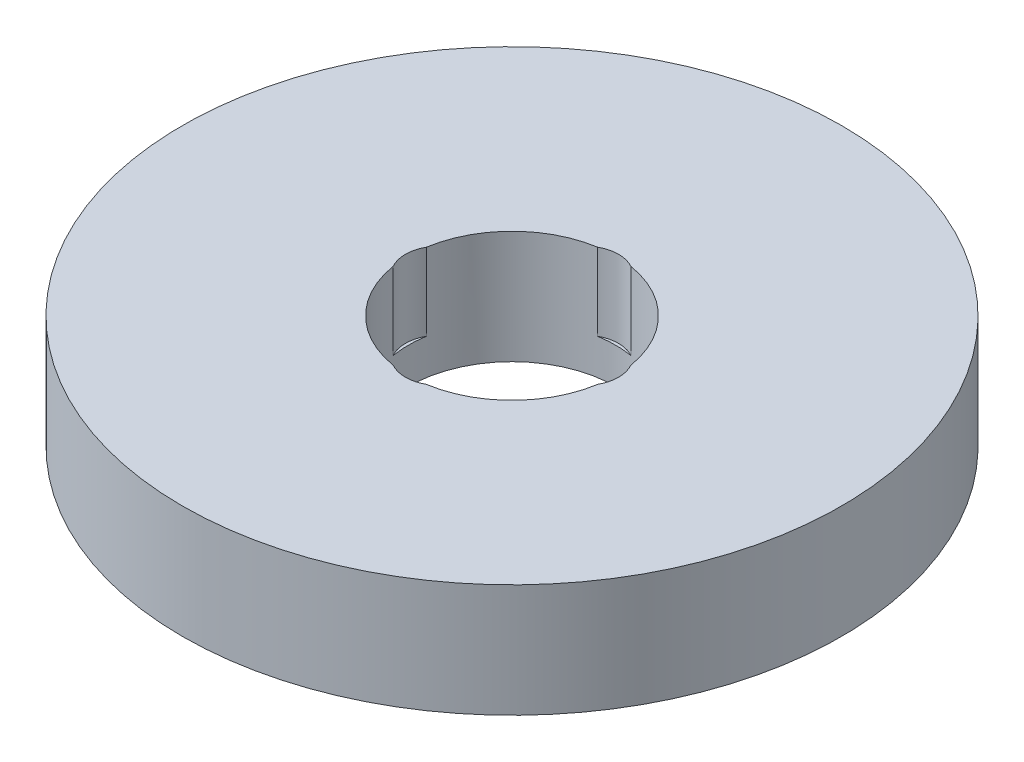
SolidWorks part; units mm, degrees
ref_plane "Front Plane" through (0, 0, 0) normal (0, 0, 1) x (1, 0, 0)
ref_plane "Top Plane" through (0, 0, 0) normal (0, 1, 0) x (1, 0, 0)
ref_plane "Right Plane" through (0, 0, 0) normal (1, 0, 0) x (0, 0, -1)
sketch "Sketch1" plane through (0, 0, 0) normal (0, 1, 0) x (1, 0, 0)
  circle A0 centre (0, 0) radius 87.5
  dimension "FLANGE_OD" = 175
extrude "Boss-Extrude1" add sketch "Sketch1" along normal blind 30
sketch "Sketch2" plane through (0, 0, 0) normal (0, 1, 0) x (1, 0, 0)
  circle A0 centre (0, 0) radius 27.5
  dimension "BORE_D" = 55
extrude "Cut-Extrude1" cut sketch "Sketch2" along normal through all
sketch "Sketch3" plane through (0, 30, 0) normal (0, 1, 0) x (1, 0, 0)
  circle A0 centre (0, 0) radius 19.2292 construction
  circle A1 centre (-19.2292, 0) radius 9.0545
  dimension "BOLT_D" = 18.109
  dimension "BOLT_PCD" = 38.4584
extrude "Cut-Extrude2" cut sketch "Sketch3" against normal blind 20.492
pattern_circular "CirPattern1" count 4 over 360 about axis through (0, 0, 0) along (0, 1, 0) of "Cut-Extrude2"
